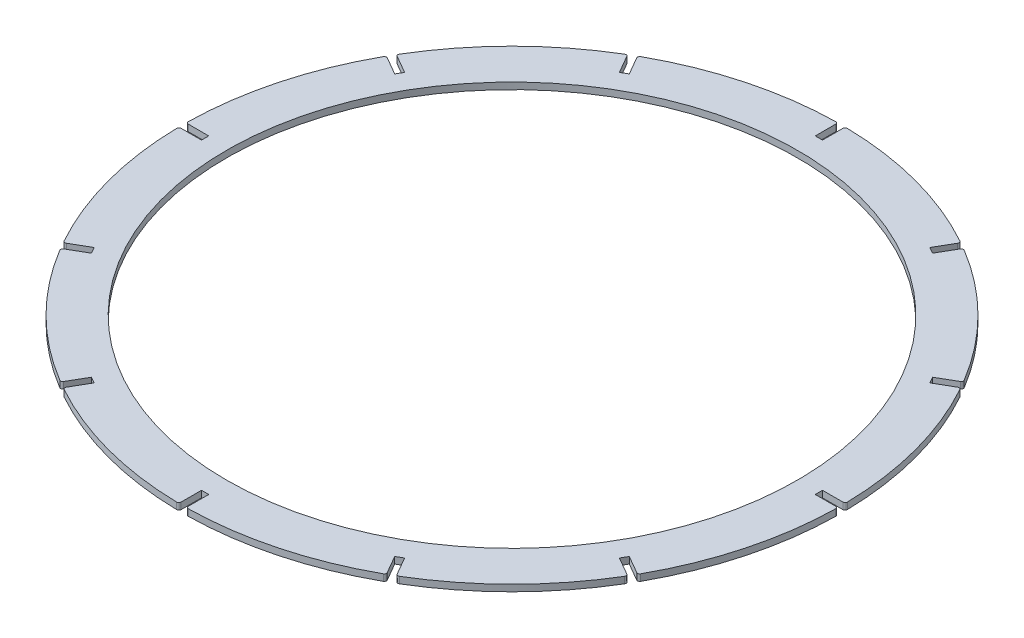
SolidWorks part; units mm, degrees
ref_plane "Front Plane" through (0, 0, 0) normal (0, 0, 1) x (1, 0, 0)
ref_plane "Top Plane" through (0, 0, 0) normal (0, 1, 0) x (1, 0, 0)
ref_plane "Right Plane" through (0, 0, 0) normal (1, 0, 0) x (0, 0, -1)
sketch "Sketch1" plane through (0, 0, 0) normal (0, 1, 0) x (1, 0, 0)
  line L1 (0, 130) -> (0, 150) construction
  circle A0 centre (0, 0) radius 150
  circle A1 centre (0, 0) radius 130
  point P7 (0, 0)
  dimension "D1" = 300
  dimension "D2" = 20
extrude "Boss-Extrude1" add sketch "Sketch1" along normal blind 3
sketch "Sketch2" plane through (0, 3, 0) normal (0, 1, 0) x (1, 0, 0)
  line L0 (0, 0) -> (0, 150) construction
  line L1 (-1.65, 139.7) -> (1.65, 139.7)
  line L2 (-1.65, 139.7) -> (-1.65, 152.3249)
  line L3 (-1.65, 152.3249) -> (1.65, 152.3249)
  line L4 (1.65, 152.3249) -> (1.65, 139.7)
  circle A0 centre (0, 0) radius 150 construction
  point P8 (0, 139.7)
  dimension "D1" = 139.7
  dimension "D2" = 3.3
extrude "Cut-Extrude1" cut sketch "Sketch2" against normal blind 3
fillet "Fillet1" radius 1 2 edges at (1.65, 1.5, -149.9909) (-1.65, 1.5, -149.9909)
pattern_circular "CirPattern1" count 12 over 360 about axis through (0, 3, 0) along (0, -1, 0) of "Fillet1", "Cut-Extrude1" reverse direction yes
